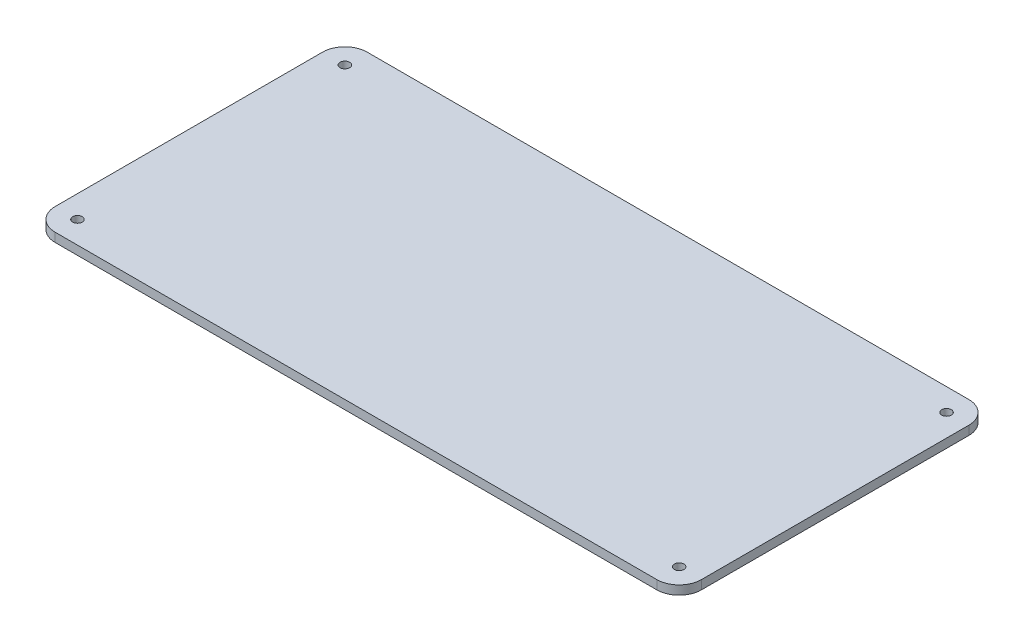
SolidWorks part; units mm, degrees
ref_plane "Front Plane" through (0, 0, 0) normal (0, 0, 1) x (1, 0, 0)
ref_plane "Top Plane" through (0, 0, 0) normal (0, 1, 0) x (1, 0, 0)
ref_plane "Right Plane" through (0, 0, 0) normal (1, 0, 0) x (0, 0, -1)
sketch "Sketch1" plane through (0, 0, 0) normal (0, 1, 0) x (1, 0, 0)
  line L0 (0, 0) -> (145, 0) construction
  line L1 (145, 0) -> (145, -60)
  line L2 (135, -70) -> (0, -70)
  line L3 (0, -70) -> (0, 0)
  line L4 (0, 0) -> (145, 0)
  arc A0 (135, -70) -> (145, -60) centre (135, -60) ccw
  circle A1 centre (135, -60) radius 2.15
  point P7 (145, -70)
  dimension "D4" = 10
  dimension "D5" = 4.3
  dimension "D1" = 145
  dimension "D2" = 70
  dimension "D3" = 145
extrude "Boss-Extrude1" add sketch "Sketch1" along normal blind 4 contours L2 A0 L1 L4 L3 A1 region at (72.2612, 0, 34.8946)
mirror "Mirror1" about plane through (0, 0, 0) normal (1, 0, 0) of "Boss-Extrude1"
mirror "Mirror2" about plane through (0, 0, 0) normal (0, 0, 1) of "Mirror1"
